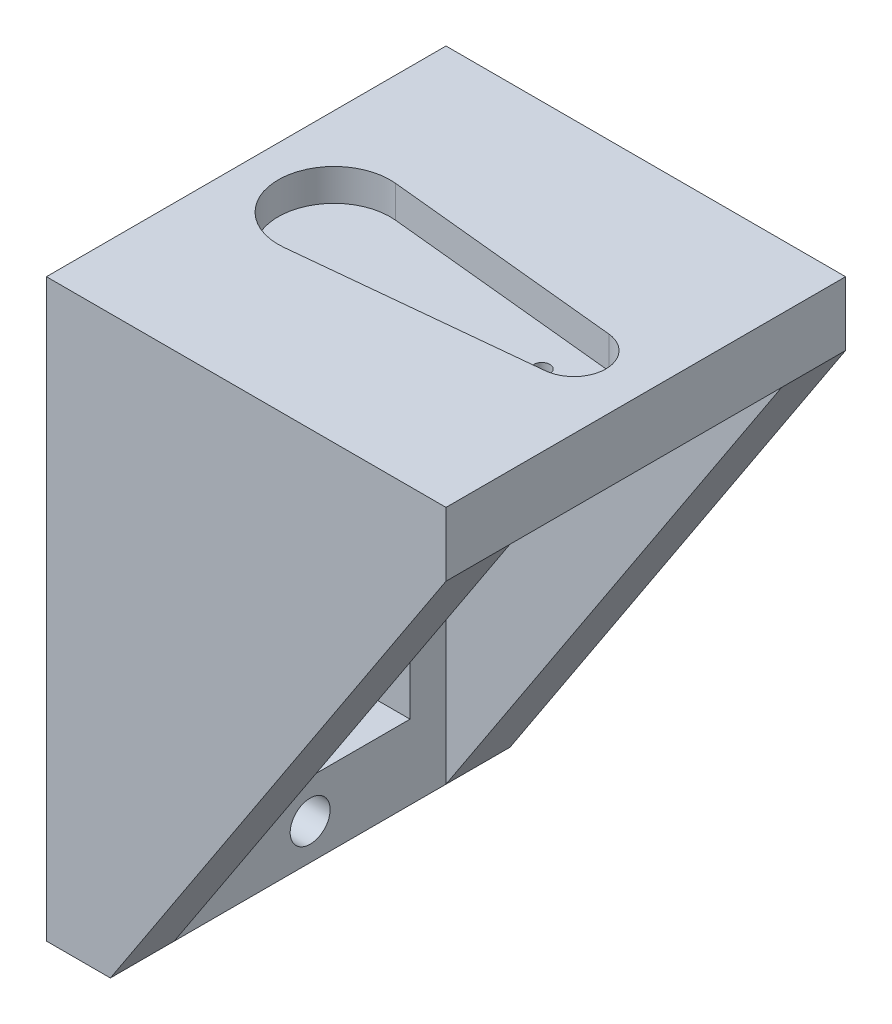
SolidWorks part; units mm, degrees
ref_plane "前视基准面" through (0, 0, 0) normal (0, 0, 1) x (1, 0, 0)
ref_plane "上视基准面" through (0, 0, 0) normal (0, 1, 0) x (1, 0, 0)
ref_plane "右视基准面" through (0, 0, 0) normal (1, 0, 0) x (0, 0, -1)
other "Configuration Table"
sketch "草图2" plane through (0, 0, 0) normal (0, 1, 0) x (1, 0, 0)
  line L1 (-12.5, 12.5) -> (12.5, 12.5)
  line L2 (-12.5, 12.5) -> (-12.5, -12.5)
  line L3 (-12.5, -12.5) -> (12.5, -12.5)
  line L4 (12.5, 12.5) -> (12.5, -12.5)
  line L5 (-12.5, 12.5) -> (12.5, -12.5) construction
  line L6 (-12.5, -12.5) -> (12.5, 12.5) construction
  point P0 (0, 0)
  dimension "D1" = 25
  dimension "D2" = 25
extrude "凸台-拉伸1" add sketch "草图2" along normal blind 4
sketch "草图3" plane through (0, 4, 0) normal (0, 1, 0) x (1, 0, 0)
  line L0 (-6.65, 3.4825) -> (8.2, 1.99)
  line L1 (-6.65, -3.4825) -> (8.2, -1.99)
  line L2 (-6.65, 3.4825) -> (-6.65, -3.4825)
  line L3 (8.2, 1.99) -> (8.2, -1.99)
  line L4 (12.5, -12.5) -> (12.5, 12.5)
  line L5 (12.5, 12.5) -> (-12.5, 12.5)
  line L6 (-12.5, 12.5) -> (-12.5, -12.5)
  line L7 (-12.5, -12.5) -> (12.5, -12.5)
  line L8 (12.5, -12.5) -> (12.5, 12.5)
  line L9 (12.5, 12.5) -> (-12.5, 12.5)
  line L10 (-12.5, 12.5) -> (-12.5, -12.5)
  line L11 (-12.5, -12.5) -> (12.5, -12.5)
  circle A0 centre (8, 0) radius 2
  circle A1 centre (-7, 0) radius 3.5
  point P13 (-12.5, 0)
  dimension "D2" = 7
  dimension "D3" = 4
  dimension "D4" = 15
  dimension "D5" = 5.5
  dimension "D1" = 0
extrude "凸台-拉伸2" add sketch "草图3" along normal blind 4 contours L2 A1 | L2 A1 | A1 L1 A0 L0 | L3 A0 | L3 A0 region at (-5.3237, 4, 0) region at (0.8041, 4, 0) region at (-8.2982, 4, 0) region at (8.9579, 4, 0) region at (7.2582, 4, 0)
sketch "草图7" plane through (0, 8, 0) normal (0, 1, 0) x (1, 0, 0)
  line L2 (-6.65, -3.4825) -> (8.2, -1.99)
  line L3 (8.2, 1.99) -> (-6.65, 3.4825)
  line L4 (-6.65, -3.4825) -> (8.2, -1.99)
  line L5 (8.2, 1.99) -> (-6.65, 3.4825)
  arc A2 (-6.65, 3.4825) -> (-6.65, -3.4825) centre (-7, 0) ccw
  arc A3 (8.2, -1.99) -> (8.2, 1.99) centre (8, 0) ccw
  arc A4 (-6.65, 3.4825) -> (-6.65, -3.4825) centre (-7, 0) ccw
  arc A5 (8.2, -1.99) -> (8.2, 1.99) centre (8, 0) ccw
  dimension "D1" = 0
extrude "切除-拉伸1" cut sketch "草图7" against normal blind 6 contours A4 L4 A5 L5
sketch "草图8" plane through (0, 2, 0) normal (0, 1, 0) x (1, 0, 0)
  line L2 (8.2, 1.99) -> (-6.65, 3.4825)
  line L3 (-6.65, -3.4825) -> (8.2, -1.99)
  line L4 (8.2, 1.99) -> (-6.65, 3.4825)
  line L5 (-6.65, -3.4825) -> (8.2, -1.99)
  circle A0 centre (6, 0) radius 0.5
  arc A2 (-6.65, 3.4825) -> (-6.65, -3.4825) centre (-7, 0) ccw
  arc A3 (8.2, -1.99) -> (8.2, 1.99) centre (8, 0) ccw
  arc A4 (-6.65, 3.4825) -> (-6.65, -3.4825) centre (-7, 0) ccw
  arc A5 (8.2, -1.99) -> (8.2, 1.99) centre (8, 0) ccw
  dimension "D2" = 1
  dimension "D3" = 13
  dimension "D1" = 0
extrude "切除-拉伸2" cut sketch "草图8" against normal blind 6 contours A0
sketch "草图11" plane through (0, 0, 0) normal (0, -1, 0) x (1, 0, 0)
  line L0 (-12.5, 12.5) -> (12.5, 12.5) construction
  line L1 (-8.4996, 12.5) -> (-12.5, 12.5)
  line L2 (-8.4996, 12.5) -> (-8.4996, -12.5)
  line L3 (-8.4996, -12.5) -> (-12.5, -12.5)
  line L4 (-12.5, 12.5) -> (-12.5, -12.5)
  line L5 (-8.4996, 12.5) -> (-12.5, -12.5) construction
  line L6 (-8.4996, -12.5) -> (-12.5, 12.5) construction
  line L8 (12.5, 12.5) -> (-8.4996, 12.5)
  line L9 (12.5, 12.5) -> (12.5, 8.5)
  line L10 (12.5, 8.5) -> (-8.4996, 8.5)
  line L11 (-8.4996, 12.5) -> (-8.4996, 8.5)
  line L12 (12.5, 12.5) -> (-8.4996, 8.5) construction
  line L13 (12.5, 8.5) -> (-8.4996, 12.5) construction
  line L14 (12.5, -12.5) -> (-8.4996, -12.5)
  line L15 (12.5, -12.5) -> (12.5, -8.5)
  line L16 (12.5, -8.5) -> (-8.4996, -8.5)
  line L17 (-8.4996, -12.5) -> (-8.4996, -8.5)
  line L18 (12.5, -12.5) -> (-8.4996, -8.5) construction
  line L19 (12.5, -8.5) -> (-8.4996, -12.5) construction
  point P4 (-10.4998, 0)
  point P11 (2.0002, 10.5)
  point P16 (2.0002, -10.5)
  line M11 (12.5, -12.5) -> (12.5, 12.5)
  line M12 (12.5, 12.5) -> (-12.5, 12.5)
  line M13 (-12.5, 12.5) -> (-12.5, -12.5)
  line M14 (-12.5, -12.5) -> (12.5, -12.5)
  dimension "D1" = 4
  dimension "D2" = 4
  dimension "D3" = 4.0004
extrude "凸台-拉伸3" add sketch "草图11" along normal blind 32 contours L10 L2 M11 M12 | L2 M12 M13 M14 | L14 L15 L16 L17 region at (-10.4998, 0, 0) region at (2.0002, 0, 10.5)
sketch "草图12" plane through (0, 0, -8.5) normal (0, 0, 1) x (1, 0, 0)
  line L0 (12.5, 0) -> (-8.4996, -32)
  line L1 (-8.4996, -32) -> (-8.4996, 0) construction
  line L2 (12.5, -32) -> (-8.4996, -32) construction
  line L3 (-8.4996, -32) -> (12.5, -32)
  line L4 (12.5, -32) -> (12.5, 0)
extrude "切除-拉伸4" cut sketch "草图12" against normal blind 32 and the other way blind 32
sketch "草图13" plane through (-8.4996, 0, 0) normal (1, 0, 0) x (0, 0, -1)
  line L0 (11.3733, -16) -> (-17.6197, -16) construction
  line L1 (0, -34.2811) -> (0, 5.8569) construction
  line L3 (6.25, -4.65) -> (-6.25, -4.65)
  line L4 (6.25, -4.65) -> (6.25, -27.35)
  line L5 (6.25, -27.35) -> (-6.25, -27.35)
  line L6 (-6.25, -4.65) -> (-6.25, -27.35)
  line L7 (6.25, -4.65) -> (-6.25, -27.35) construction
  line L8 (6.25, -27.35) -> (-6.25, -4.65) construction
  circle A0 centre (0, -29.75) radius 1.25
  circle A1 centre (0, -2.25) radius 1.25
  point P5 (0, -16)
  dimension "D3" = 27.5
  dimension "D4" = 2.5
  dimension "D1" = 22.7
  dimension "D2" = 12.5
extrude "切除-拉伸5" cut sketch "草图13" against normal through all
equation "\"27.5、\"=27.9175"
equation "\"2，5\"=3.73119"
